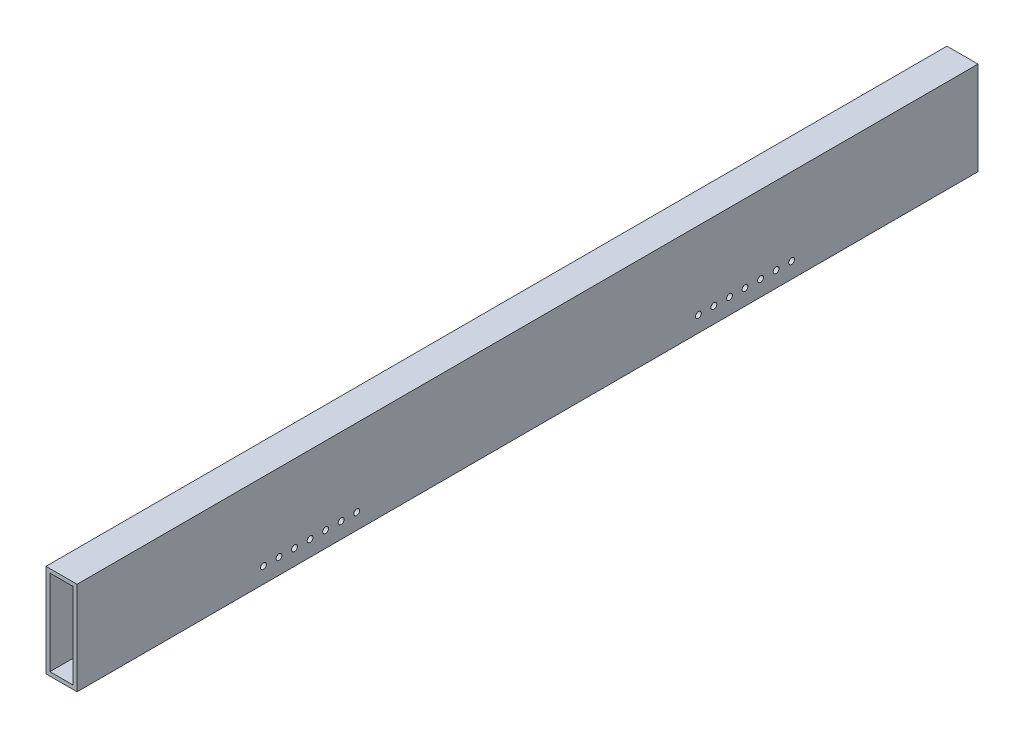
SolidWorks part; units mm, degrees
ref_plane "Front Plane" through (0, 0, 0) normal (0, 0, 1) x (1, 0, 0)
ref_plane "Top Plane" through (0, 0, 0) normal (0, 1, 0) x (1, 0, 0)
ref_plane "Right Plane" through (0, 0, 0) normal (1, 0, 0) x (0, 0, -1)
sketch "Sketch1" plane through (0, 0, 0) normal (0, 0, 1) x (1, 0, 0)
  line L1 (-12.7, -38.1) -> (12.7, -38.1)
  line L2 (-12.7, -38.1) -> (-12.7, 38.1)
  line L3 (-12.7, 38.1) -> (12.7, 38.1)
  line L4 (12.7, -38.1) -> (12.7, 38.1)
  line L5 (-12.7, -38.1) -> (12.7, 38.1) construction
  line L6 (-12.7, 38.1) -> (12.7, -38.1) construction
  point P0 (0, 0)
  dimension "D1" = 25.4
  dimension "D2" = 76.2
extrude "Boss-Extrude1" add sketch "Sketch1" along normal mid plane 736.6
shell "Shell1" thickness 3.175 removed face at (0, 0, -368.3) removed face at (0, 0, 368.3)
sketch "Sketch3" plane through (12.7, 0, 0) normal (1, 0, 0) x (0, 0, -1)
  line L0 (368.3, -38.1) -> (368.3, 38.1) construction
  line L1 (-368.3, -38.1) -> (368.3, -38.1) construction
  line L2 (0, -53.276) -> (0, 47.534) construction
  circle A0 centre (215.9, -25.1959) radius 2.3813
  circle A1 centre (203.2, -25.1959) radius 2.3813
  circle A2 centre (190.5, -25.1959) radius 2.3813
  circle A3 centre (177.8, -25.1959) radius 2.3813
  circle A4 centre (165.1, -25.1959) radius 2.3813
  circle A5 centre (152.4, -25.1959) radius 2.3813
  circle A6 centre (139.7, -25.1959) radius 2.3813
  circle A7 centre (-139.7, -25.1959) radius 2.3813
  circle A8 centre (-152.4, -25.1959) radius 2.3813
  circle A9 centre (-165.1, -25.1959) radius 2.3813
  circle A10 centre (-203.2, -25.1959) radius 2.3813
  circle A11 centre (-177.8, -25.1959) radius 2.3813
  circle A12 centre (-215.9, -25.1959) radius 2.3813
  circle A13 centre (-190.5, -25.1959) radius 2.3813
  dimension "D1" = 4.7625
  dimension "D3" = 12.7
  dimension "D4" = 12.7
  dimension "D5" = 12.7
  dimension "D6" = 12.7
  dimension "D7" = 12.7
  dimension "D8" = 12.7
  dimension "D9" = 12.9041
  dimension "D2" = 152.4
extrude "Cut-Extrude2" cut sketch "Sketch3" against normal up to next
equation "\"robotwidth\"= 29in"
equation "\"D1@Boss-Extrude1\"=\"robotwidth\""
